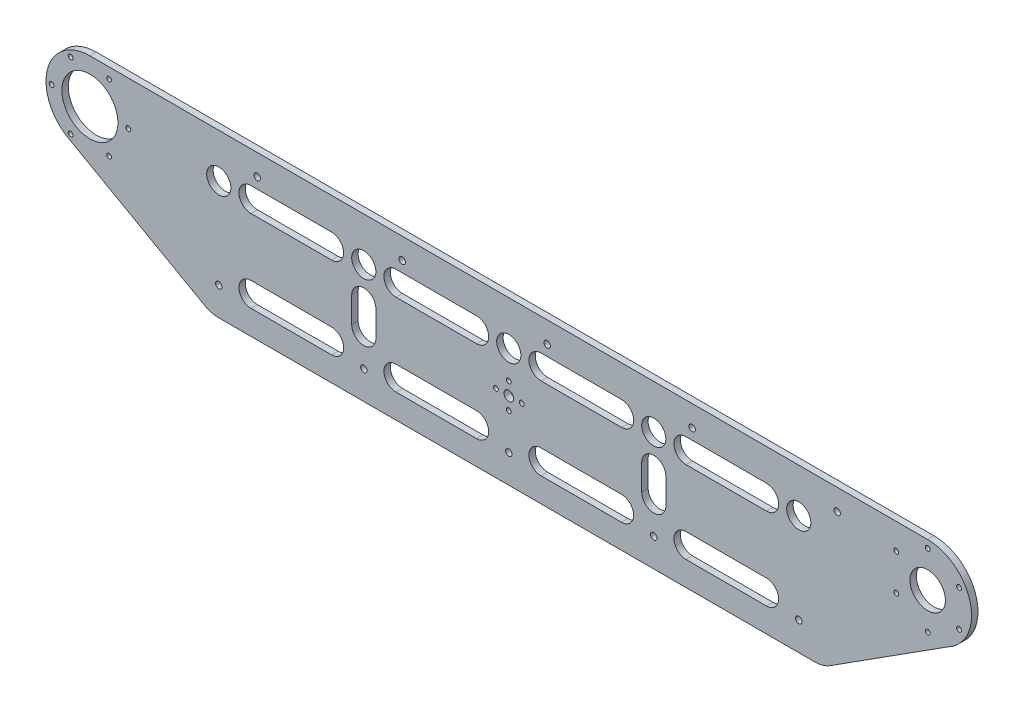
SolidWorks part; units mm, degrees
material "3.1305 (EN-AW 2117)"
ref_plane "Alzado" through (0, 0, 0) normal (0, 0, 1) x (1, 0, 0)
ref_plane "Planta" through (0, 0, 0) normal (0, 1, 0) x (1, 0, 0)
ref_plane "Vista lateral" through (0, 0, 0) normal (1, 0, 0) x (0, 0, -1)
sketch "Croquis1" plane through (0, 0, 0) normal (0, 0, 1) x (1, 0, 0)
  line L4 (102.5, 23.182) -> (90, 21.1607) construction
  line L5 (90, -23.8925) -> (180, -23.8925) construction
  line L6 (-102.5, -9.9669) -> (-83.0991, -6.8298) construction
  line L7 (-215.9366, -23.8925) -> (-260, -23.8925) construction
  line L8 (-90, -23.8925) -> (-92, -23.8925) construction
  line L9 (-188.6184, -23.8925) -> (-182, -23.8925) construction
  line L10 (-260, -23.8925) -> (-260, 1.2874) construction
  line L11 (-179.1956, -41.4802) -> (179.1956, -41.4802)
  line L12 (-260, 32.1075) -> (-180, -23.8925) construction
  line L18 (179.1956, -41.4802) -> (190.0108, -41.4802)
  line L19 (0, -23.8925) -> (-12.5, -23.8925) construction
  line L20 (-180, -23.8925) -> (-167.5, -23.8925) construction
  line L21 (-90, -23.8925) -> (-92, -23.8925) construction
  line L24 (-90, -23.8925) -> (-90, 32.1075) construction
  line L28 (-182, -23.9062) -> (-188.6184, -23.8925) construction
  line L30 (-180, -23.8925) -> (-196.3846, -12.4232) construction
  line L31 (-196.3846, -12.4232) -> (-221.6689, 5.2758) construction
  line L32 (-260, 32.1075) -> (-243.6154, 20.6383) construction
  line L36 (-272.7427, 8.0318) -> (-188.6256, -39.2409)
  line L41 (-90, 32.1075) -> (-90, 12.1075) construction
  line L42 (-90, -23.8925) -> (-90, -3.8925) construction
  line L43 (-82.5, 12.1075) -> (-82.5, -3.8925)
  line L44 (-97.5, 12.1075) -> (-97.5, -3.8925)
  line L45 (-90, 44.6075) -> (-90, -11.3925) construction
  line L46 (-20, 24.6075) -> (-70, 24.6075)
  line L47 (-20, 39.6075) -> (-70, 39.6075)
  line L48 (287.24, 32.1075) -> (284.0739, 32.1075) construction
  line L50 (260, 59.3475) -> (260, 32.1075) construction
  line L51 (90, 44.6075) -> (90, -11.3925) construction
  line L52 (90, -23.8925) -> (90, -3.8925) construction
  line L53 (90, 32.1075) -> (90, 12.1075) construction
  line L54 (260, 32.1075) -> (260, 39.1075) construction
  line L55 (160, -26.3925) -> (110, -26.3925)
  line L56 (-260, 4.1) -> (-260, 32.1075) construction
  line L57 (160, -11.3925) -> (110, -11.3925)
  line L58 (20, -11.3925) -> (70, -11.3925)
  line L59 (20, 39.6075) -> (70, 39.6075)
  line L60 (260, 32.1075) -> (260, 25.1075) construction
  line L65 (-160, 39.6075) -> (-110, 39.6075)
  line L66 (-160, 24.6075) -> (-110, 24.6075)
  line L67 (20, -26.3925) -> (70, -26.3925)
  line L83 (-260, 59.3475) -> (260, 59.3475)
  line L87 (-287.24, 32.1075) -> (-284.0739, 32.1075) construction
  line L88 (-20, -26.3925) -> (-70, -26.3925)
  line L89 (160, 24.6075) -> (110, 24.6075)
  line L90 (-20, -11.3925) -> (-70, -11.3925)
  line L91 (-167.5, -23.8925) -> (-180, -23.8925) construction
  line L92 (-102.5, 23.182) -> (-90, 21.1607) construction
  line L93 (160, 39.6075) -> (110, 39.6075)
  line L94 (-6.5, 6.6075) -> (-141.7981, 6.6075) construction
  line L95 (90, -23.8925) -> (88, -23.8925) construction
  line L96 (-135, 39.6075) -> (-135, 14.7545) construction
  line L97 (135, 39.6075) -> (135, 20.6383) construction
  line L98 (-88, -23.8925) -> (-90, -23.8925) construction
  line L99 (-160, -26.3925) -> (-110, -26.3925)
  line L100 (-83.0991, -6.8298) -> (-102.5, -9.9669) construction
  line L101 (-90, 21.1607) -> (-102.5, 23.182) construction
  line L102 (-160, -11.3925) -> (-110, -11.3925)
  line L103 (83.0991, -6.8298) -> (102.5, -9.9669) construction
  line L106 (90, 21.1607) -> (102.5, 23.182) construction
  line L115 (90, -23.8925) -> (90, 32.1075) construction
  line L116 (90, -23.8925) -> (92, -23.8925) construction
  line L119 (265.4417, 3.373) -> (265.4184, 3.7892) construction
  line L121 (90, -23.8925) -> (92, -23.8925) construction
  line L122 (102.5, -9.9669) -> (83.0991, -6.8298) construction
  line L124 (20, 24.6075) -> (70, 24.6075)
  line L125 (97.5, 12.1075) -> (97.5, -3.8925)
  line L126 (82.5, 12.1075) -> (82.5, -3.8925)
  line L127 (272.7427, 8.0318) -> (199.4836, -38.7153)
  circle A5 centre (0, -23.8925) radius 2
  circle A6 centre (-90, -23.8925) radius 2
  circle A7 centre (-180, -23.8925) radius 2
  circle A25 centre (-90, 32.1075) radius 7.5
  arc A26 (-82.5, 12.1075) -> (-97.5, 12.1075) centre (-90, 12.1075) ccw
  arc A27 (-97.5, -3.8925) -> (-82.5, -3.8925) centre (-90, -3.8925) ccw
  arc A28 (-20, 39.6075) -> (-20, 24.6075) centre (-20, 32.1075) cw
  arc A29 (-70, 24.6075) -> (-70, 39.6075) centre (-70, 32.1075) cw
  circle A30 centre (0, 32.1075) radius 7.5
  circle A51 centre (-260, 32.1075) radius 17.4
  arc A52 (-260, 59.3475) -> (-272.7427, 8.0318) centre (-260, 32.1075) ccw
  arc A54 (-188.6256, -39.2409) -> (-179.1956, -41.4802) centre (-180, -23.8925) ccw
  arc A56 (260, 59.3475) -> (272.7427, 8.0318) centre (260, 32.1075) cw
  circle A57 centre (260, 32.1075) radius 11
  arc A58 (70, 24.6075) -> (70, 39.6075) centre (70, 32.1075) ccw
  arc A59 (20, 39.6075) -> (20, 24.6075) centre (20, 32.1075) ccw
  arc A60 (97.5, -3.8925) -> (82.5, -3.8925) centre (90, -3.8925) cw
  arc A61 (82.5, 12.1075) -> (97.5, 12.1075) centre (90, 12.1075) cw
  circle A62 centre (90, 32.1075) radius 7.5
  circle A66 centre (90, -23.8925) radius 2
  arc A71 (-160, 39.6075) -> (-160, 24.6075) centre (-160, 32.1075) ccw
  arc A72 (-110, 24.6075) -> (-110, 39.6075) centre (-110, 32.1075) ccw
  arc A73 (160, 39.6075) -> (160, 24.6075) centre (160, 32.1075) cw
  arc A74 (110, 24.6075) -> (110, 39.6075) centre (110, 32.1075) cw
  circle A75 centre (-180, 32.1075) radius 7.5
  circle A76 centre (180, 32.1075) radius 7.5
  circle A77 centre (-8, 6.6075) radius 1.5
  circle A78 centre (0, 14.6075) radius 1.5
  circle A79 centre (8, 6.6075) radius 1.5
  circle A80 centre (0, -1.3925) radius 1.5
  circle A81 centre (0, 6.6075) radius 3
  circle A82 centre (180, -23.8925) radius 2
  arc A83 (199.4836, -38.7153) -> (190.0108, -41.4802) centre (190.0108, -23.8702) cw
  arc A84 (160, -26.3925) -> (160, -11.3925) centre (160, -18.8925) ccw
  arc A85 (110, -11.3925) -> (110, -26.3925) centre (110, -18.8925) ccw
  arc A86 (20, -26.3925) -> (20, -11.3925) centre (20, -18.8925) cw
  arc A87 (70, -11.3925) -> (70, -26.3925) centre (70, -18.8925) cw
  arc A88 (-20, -26.3925) -> (-20, -11.3925) centre (-20, -18.8925) ccw
  arc A89 (-70, -11.3925) -> (-70, -26.3925) centre (-70, -18.8925) ccw
  arc A90 (-110, -11.3925) -> (-110, -26.3925) centre (-110, -18.8925) cw
  arc A91 (-160, -26.3925) -> (-160, -11.3925) centre (-160, -18.8925) cw
  point P0 (0, 6.6075)
  dimension "D5" = 4
  dimension "D7" = 4
  dimension "D9" = 4
  dimension "D11" = 22
  dimension "D10" = 54.48
  dimension "D12" = 27.24
  dimension "D15" = 7
  dimension "D16" = 7
  dimension "D18" = 4
  dimension "D20" = 6
  dimension "D21" = 34.8
  dimension "D23" = 4
  dimension "D24" = 90
  dimension "D25" = 15
  dimension "D28" = 15
  dimension "D30" = 15
  dimension "D31" = 15
  dimension "D33" = 17.61
  dimension "D17" = 3
  dimension "D32" = 4
  dimension "D4" = 30.5
  dimension "D6" = 90
  dimension "D8" = 90
  dimension "D13" = 80
  dimension "D14" = 56
  dimension "D19" = 20
  dimension "D22" = 20
  dimension "D26" = 20
  dimension "D27" = 56
  dimension "D29" = 20
extrude "Saliente-Extruir1" add sketch "Croquis1" along normal mid plane 4
sketch "Croquis2" plane through (0, 0, 2) normal (0, 0, 1) x (1, 0, 0)
  line L0 (-287.24, 32.1075) -> (-283.74, 32.1075) construction
  line L1 (-260, 32.1075) -> (-271.95, 52.8055) construction
  line L2 (-260, 32.1075) -> (-248.05, 52.8055) construction
  line L3 (-260, 32.1075) -> (-271.95, 11.4095) construction
  line L4 (-260, 32.1075) -> (-248.05, 11.4095) construction
  line L5 (-260, 32.1075) -> (-236.1, 32.1075) construction
  line L6 (-260, 32.1075) -> (-283.74, 32.1075) construction
  arc A0 (-260, 59.3475) -> (-272.7427, 8.0318) centre (-260, 32.1075) ccw construction
  circle A1 centre (-283.74, 32.1075) radius 1.5
  circle A3 centre (-271.95, 52.8055) radius 1.5
  circle A4 centre (-248.05, 52.8055) radius 1.5
  circle A5 centre (-236.1, 32.1075) radius 1.5
  circle A6 centre (-248.05, 11.4095) radius 1.5
  circle A7 centre (-271.95, 11.4095) radius 1.5
  dimension "D2" = 3
  dimension "D12" = 3
  dimension "D13" = 3
  dimension "D14" = 3
  dimension "D15" = 3
  dimension "D16" = 3
  dimension "D1" = 3.5
  dimension "D3" = 60
  dimension "D4" = 60
  dimension "D5" = 60
  dimension "D6" = 60
  dimension "D7" = 23.9
  dimension "D8" = 23.9
  dimension "D9" = 23.9
  dimension "D10" = 23.9
  dimension "D11" = 23.9
extrude "Cortar-Extruir1" cut sketch "Croquis2" against normal blind 10
sketch "Croquis3" plane through (0, 0, 2) normal (0, 0, 1) x (1, 0, 0)
  line L0 (260, 32.1075) -> (260, 54.6075) construction
  circle A0 centre (260, 54.6075) radius 1.5
  circle A1 centre (279.4856, 43.3575) radius 1.5
  circle A2 centre (279.4856, 20.8575) radius 1.5
  circle A3 centre (260, 9.6075) radius 1.5
  circle A4 centre (240.5144, 20.8575) radius 1.5
  circle A5 centre (240.5144, 43.3575) radius 1.5
  dimension "D2" = 3
  dimension "D1" = 22.5
  dimension "D3" = 6
extrude "Cortar-Extruir2" cut sketch "Croquis3" against normal blind 10
sketch "Croquis4" plane through (0, 0, 2) normal (0, 0, 1) x (1, 0, 0)
  line L0 (240.5144, 43.3575) -> (240.5144, 46.2175) construction
  line L1 (-156.1656, 44.2175) -> (-156.1656, 46.2175) construction
  line L2 (-156.1656, 46.2175) -> (-66.1656, 46.2175) construction
  line L3 (-66.1656, 46.2175) -> (23.8344, 46.2175) construction
  line L4 (23.8344, 46.2175) -> (113.8344, 46.2175) construction
  line L5 (113.8344, 46.2175) -> (203.8344, 46.2175) construction
  line L6 (240.5144, 46.2175) -> (203.8344, 46.2175) construction
  circle A0 centre (-156.1656, 46.2175) radius 2
  circle A1 centre (-66.1656, 46.2175) radius 2
  circle A2 centre (23.8344, 46.2175) radius 2
  circle A3 centre (113.8344, 46.2175) radius 2
  circle A4 centre (203.8344, 46.2175) radius 2
  dimension "D3" = 4
  dimension "D8" = 4
  dimension "D9" = 4
  dimension "D10" = 4
  dimension "D11" = 4
  dimension "D2" = 2.86
  dimension "D4" = 90
  dimension "D5" = 90
  dimension "D6" = 90
  dimension "D7" = 90
  dimension "D12" = 36.68
extrude "Cortar-Extruir3" cut sketch "Croquis4" against normal blind 10
